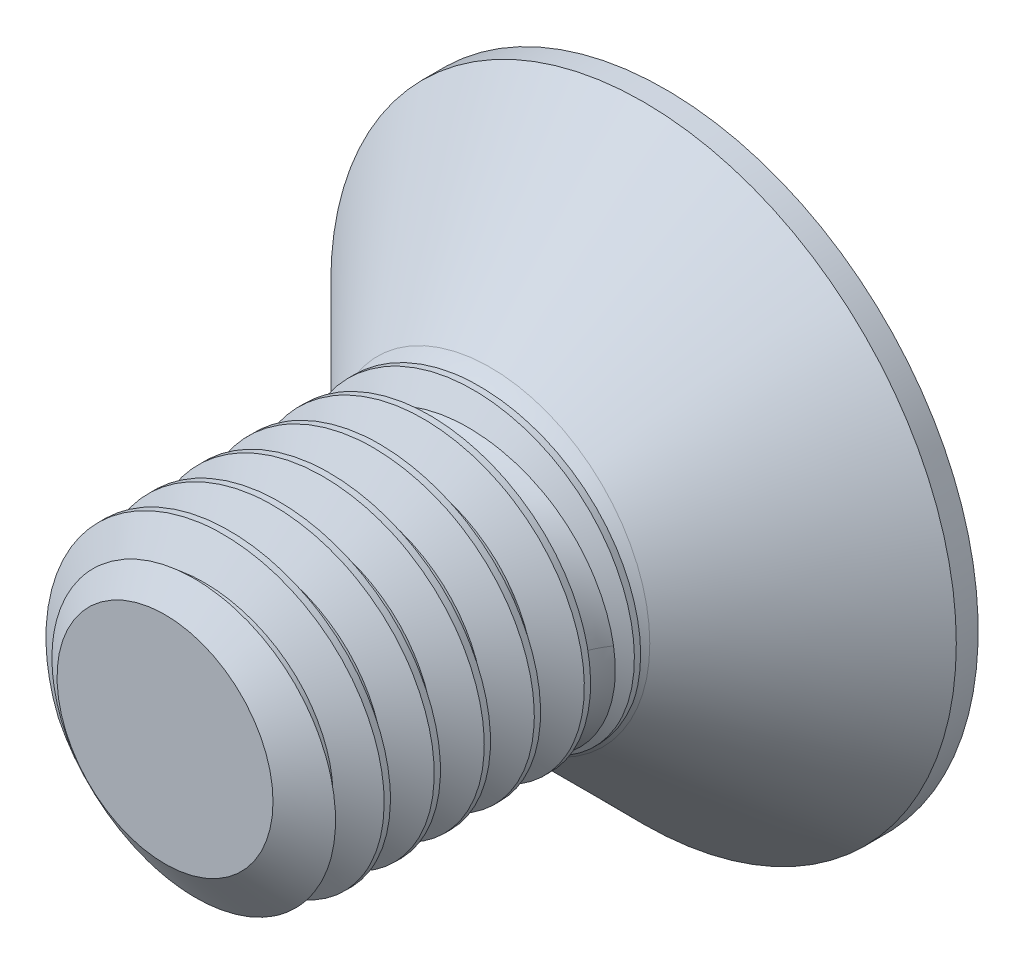
SolidWorks part; units mm, degrees
ref_plane "Front Plane" through (0, 0, 0) normal (0, 0, 1) x (1, 0, 0)
ref_plane "Top Plane" through (0, 0, 0) normal (0, 1, 0) x (1, 0, 0)
ref_plane "Right Plane" through (0, 0, 0) normal (1, 0, 0) x (0, 0, -1)
sketch "Sketch1" plane through (0, 0, 0) normal (0, 0, 1) x (1, 0, 0)
  circle A0 centre (0, 0) radius 2.5
  dimension "OD" = 5
extrude "Extrude1" add sketch "Sketch1" against normal blind 8
sketch "Sketch2" plane through (0, 0, 0) normal (0, 0, 1) x (1, 0, 0)
  circle A0 centre (0, 0) radius 2.5 construction
  circle A1 centre (0, 0) radius 2.5
curve "Helix/Spiral1" pitch 0.8 height 8.8 turns 11 parameters "pitch"=0.8
sketch "Sketch3" plane through (0, 0, 0) normal (1, 0, 0) x (0, 0, -1)
  line L0 (-0.7, 2.5) -> (-0.4, 1.9804)
  line L1 (-0.4, 1.9804) -> (-0.3, 1.9804)
  line L2 (-0.3, 1.9804) -> (0, 2.5)
  line L3 (-0.7, 2.5) -> (0, 2.5)
  line L4 (-0.35, 2.5) -> (-0.35, 1.9804) construction
  line L5 (-0.55, 2.2402) -> (-0.15, 2.2402) construction
  line L6 (0, 2.5) -> (0, -2.5) construction
  dimension "D1" = 0.1
  dimension "D2" = 0.4
  dimension "D3" = 60
sweep "Cut-Sweep1" cut profiles "Sketch3" path "Helix/Spiral1"
sketch "Sketch4" plane through (0, 0, 0) normal (1, 0, 0) x (0, 0, -1)
  line L0 (0.5417, 2.5) -> (0, 1.7264)
  line L1 (0, 1.7264) -> (0, 2.5)
  line L2 (0.5417, 2.5) -> (0, 2.5)
  line L3 (-0.7, 2.5) -> (0, 2.5) construction
  line L4 (0, 0) -> (7.0209, 0) construction
  dimension "D1" = 55
  dimension "D2" = 0.254
revolve "Cut-Revolve1" cut sketch "Sketch4" angle 360 about L4
sketch "Sketch5" plane through (0, 0, 0) normal (1, 0, 0) x (0, 0, -1)
  line L0 (8, -1.991) -> (8, 1.7838) construction
  line L1 (8, 2.55) -> (18.1906, 2.55)
  line L2 (8, 2.55) -> (8, 0)
  line L3 (8, 0) -> (18, 0)
  line L4 (18, 2.2198) -> (18, 0)
  line L5 (18.1906, 2.55) -> (18, 2.2198)
  line L6 (0, 0) -> (9.9695, 0) construction
  point P3 (18, 2.55)
  point P10 (18, 2.55)
  dimension "D1" = 0.3302
  dimension "Thread min" = 18
  dimension "D2" = 0.05
  dimension "D3" = 30
revolve "partially thread" [suppressed] add sketch "Sketch5" angle 360 about L6
sketch "Sketch6" plane through (0, 0, -8) normal (0, 0, -1) x (-1, 0, 0)
  circle A0 centre (0, 0) radius 5
  dimension "head dia" = 10
extrude "Extrude2" add sketch "Sketch6" against normal blind 2.8
sketch "Sketch10" plane through (0, 0, 0) normal (1, 0, 0) x (0, 0, -1)
  line L0 (7.65, -5) -> (5.2, -2.55)
  line L1 (5.2, -2.55) -> (5.2, -5)
  line L2 (7.65, -5) -> (5.2, -5)
  line L3 (0, 0) -> (5.2, 0) construction
  line L4 (5.2, 5) -> (5.2, -5) construction
  line L5 (7.65, 5) -> (5.2, 5) construction
  line L6 (5.2, 2.55) -> (5.2, 5) construction
  line L7 (7.65, 5) -> (5.2, 2.55) construction
  line L8 (5.2, 5) -> (5.2, -5) construction
  line L9 (5.2, 2.55) -> (5.2, -2.55) construction
  dimension "D1" = 45
  dimension "D2" = 0.05
revolve "Cut-Revolve2" cut sketch "Sketch10" angle 360 about L3
sketch "Sketch11" plane through (0, 0, 0) normal (1, 0, 0) x (0, 0, -1)
  line L0 (-0.4, 1.9804) -> (-0.3, 1.9804) construction
  line L1 (7.65, 5) -> (5.2, 2.55) construction
  line L2 (3.8248, 1.9804) -> (3.8248, 0)
  line L3 (3.8248, 0) -> (5.2, 0)
  line L4 (5.2, 2.55) -> (5.2, 0)
  line L5 (0, 0) -> (5.2, 0) construction
  arc A0 (5.2, 2.55) -> (3.8248, 1.9804) centre (3.8248, 3.9252) cw
revolve "Revolve1" add sketch "Sketch11" angle 360 about L3
sketch "Sketch7" plane through (0, 0, -8) normal (0, 0, 1) x (1, 0, 0)
  line L1 (0, 1.7321) -> (-1.5, 0.866)
  line L2 (-1.5, 0.866) -> (-1.5, -0.866)
  line L3 (-1.5, -0.866) -> (0, -1.7321)
  line L4 (0, -1.7321) -> (1.5, -0.866)
  line L5 (1.5, -0.866) -> (1.5, 0.866)
  line L6 (1.5, 0.866) -> (0, 1.7321)
  circle A0 centre (0, 0) radius 1.5 construction
  dimension "hex dia" = 3
extrude "Cut-Extrude1" cut sketch "Sketch7" along normal blind 2.25
sketch "Sketch8" plane through (0, 0, -8) normal (0, 0, 1) x (1, 0, 0)
  circle A0 centre (0, 0) radius 1.7321
extrude "Cut-Extrude2" cut sketch "Sketch8" along normal through all draft 45
sketch "Sketch9" plane through (0, 0, 0) normal (1, 0, 0) x (0, 0, -1)
  line L0 (0, 2.5) -> (0, -2.5) construction
  line L1 (4.4, 2.5) -> (4.4, -2.5) construction
  line L2 (5.2, 2.5) -> (5.2, -2.5) construction
  line L3 (5.2, -2.55) -> (5.2, -5) construction
  dimension "D1" = 4.4
equation "\"D3@Helix/Spiral1\" = \"screw length@Extrude1\"+\"pitch@Helix/Spiral1\""
equation "\"D1@Sketch3\" = \"pitch@Helix/Spiral1\"*.125"
equation "\"D2@Sketch3\" = \"pitch@Helix/Spiral1\"*.5"
equation "\"D1@Cut-Extrude1\" = \"hex dia@Sketch7\"*.75"
equation "\"D1@Sketch9\" = \"pitch@Helix/Spiral1\"*5.5"
equation "\"D2@Sketch10\" = \"D2@Sketch5\""
